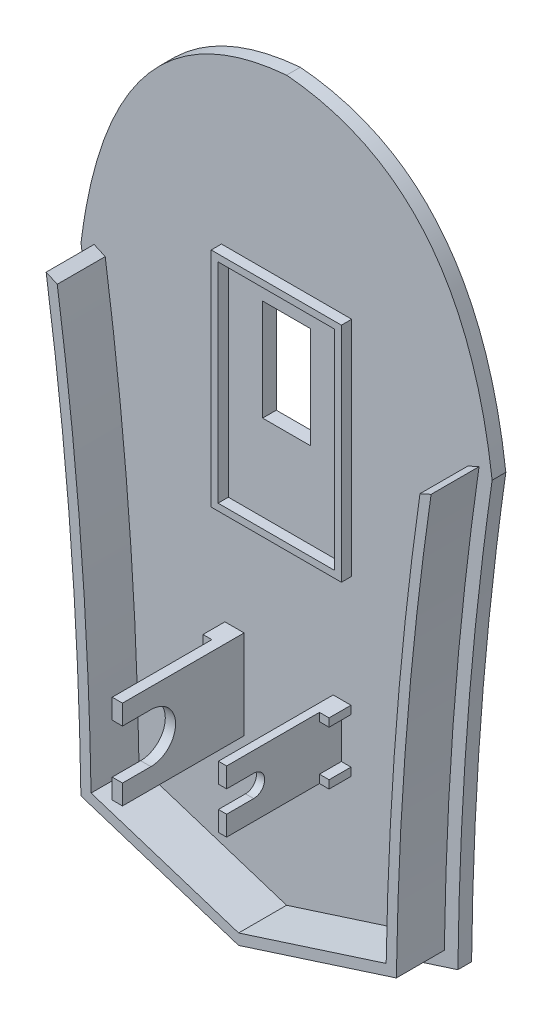
SolidWorks part; units mm, degrees
ref_plane "Přední rovina" through (0, 0, 0) normal (0, 0, 1) x (1, 0, 0)
ref_plane "Horní rovina" through (0, 0, 0) normal (0, 1, 0) x (1, 0, 0)
ref_plane "Pravá rovina" through (0, 0, 0) normal (1, 0, 0) x (0, 0, -1)
sketch "Skica3" plane through (0, 0, 0) normal (0, 0, 1) x (1, 0, 0)
  line L0 (0, 108.5972) -> (0, 0) construction
  line L1 (0, 0) -> (25, 8.0276)
  line L2 (0, 0) -> (-25, 8.0276)
  spline S0 degree 2 poles (25, 8.0276) (25.363, 40.4056) (30, 72.3988) knots 0 0 0 1 1 1
  spline S1 degree 2 poles (30, 72.3988) (25.8102, 106.3932) (0, 108.5972) knots 0 0 0 1 1 1
  spline S2 degree 2 poles (-25, 8.0276) (-25.363, 40.4056) (-30, 72.3988) knots 0 0 0 1 1 1
  spline S3 degree 2 poles (-30, 72.3988) (-25.8102, 106.3932) (0, 108.5972) knots 0 0 0 1 1 1
  dimension "D1" = 36.1984
  dimension "D2" = 62.7645
  dimension "D3" = 100.5695
  dimension "D4" = 108.5972
  dimension "D5" = 60
  dimension "D6" = 50
  dimension "D7" = 55
  dimension "D8" = 7.7177
  dimension "D9" = 1.523
extrude "Přidat vysunutím3" add sketch "Skica3" along normal blind 2
sketch "Skica5" plane through (0, 0, 2) normal (0, 0, 1) x (1, 0, 0)
  line L0 (0, 69.8773) -> (0, 10) construction
  line L3 (-8.5, 81.5) -> (8.5, 81.5)
  line L4 (8.5, 81.5) -> (8.5, 51)
  line L5 (8.5, 51) -> (0, 51)
  line L6 (-9.5, 50) -> (9.5, 50)
  line L7 (9.5, 50) -> (9.5, 82.5)
  line L8 (9.5, 82.5) -> (-9.5, 82.5)
  line L9 (-9.5, 50) -> (-9.5, 82.5)
  line L10 (-8.5, 51) -> (0, 51)
  line L11 (-8.5, 81.5) -> (-8.5, 51)
  point P6 (0, 82.5)
  point P12 (4.25, 51)
  point P15 (9.5, 66.25)
  point P19 (0, 50)
  point P20 (0, 81.5)
  dimension "D1" = 1
  dimension "D2" = 1
  dimension "D3" = 1
  dimension "D4" = 9.5
  dimension "D5" = 32.5
  dimension "D6" = 50
sketch "Skica6" plane through (0, 0, 2) normal (0, 0, 1) x (1, 0, 0)
  line L0 (-9.5, 50) -> (9.5, 50) construction
  line L1 (8, 33.66) -> (8, 24.66)
  line L2 (8, 33.66) -> (6.8, 33.66)
  line L3 (6.8, 33.66) -> (6.8, 24.66)
  line L4 (8, 24.66) -> (6.8, 24.66)
  line L5 (-6.2, 35) -> (-6.2, 22)
  line L6 (-6.2, 35) -> (-7.7, 35)
  line L7 (-7.7, 35) -> (-7.7, 22)
  line L8 (-6.2, 22) -> (-7.7, 22)
  line L9 (-9.5, 50) -> (-9.5, 82.5) construction
  line L10 (9.5, 50) -> (9.5, 82.5) construction
  point P15 (7.4, 24.66)
  dimension "D2" = 13
  dimension "D3" = 9
  dimension "D4" = 16.34
  dimension "D5" = 1.2
  dimension "D6" = 15
  dimension "D7" = 3.3
  dimension "D8" = 1.5
  dimension "D9" = 2.7
  dimension "D10" = 2.1
  dimension "D11" = 28
extrude "Přidat vysunutím4" add sketch "Skica5" along normal blind 1.5
extrude "Přidat vysunutím5" add sketch "Skica6" along normal blind 17.75 contours L5 L8 L7 L6
extrude "Přidat vysunutím6" add sketch "Skica6<4>" along normal blind 16.75 contours L4 L1 L2 L3 region at (7.4, 29.16, 2)
sketch "Skica6<4>" plane through (0, 0, 2) normal (0, 0, 1) x (1, 0, 0) same geometry as "Skica6"
sketch "Skica9" plane through (0, 0, 2) normal (0, 0, 1) x (1, 0, 0)
  line L0 (8, 33.66) -> (8, 24.66) construction
  line L1 (8, 33.66) -> (8, 32.4771)
  line L2 (8, 33.66) -> (9.4, 33.66)
  line L3 (9.4, 33.66) -> (9.4, 32.4771)
  line L4 (8, 32.4771) -> (9.4, 32.4771)
  line L5 (8, 24.66) -> (8, 25.8416)
  line L6 (8, 24.66) -> (9.4, 24.66)
  line L7 (9.4, 24.66) -> (9.4, 25.8416)
  line L8 (8, 25.8416) -> (9.4, 25.8416)
  line L9 (-7.7, 22) -> (-7.7, 23.3695)
  line L10 (-7.7, 22) -> (-9, 22)
  line L11 (-9, 22) -> (-9, 23.3695)
  line L12 (-7.7, 23.3695) -> (-9, 23.3695)
  line L13 (-7.7, 35) -> (-7.7, 33.66)
  line L14 (-7.7, 35) -> (-9, 35)
  line L15 (-9, 35) -> (-9, 33.66)
  line L16 (-7.7, 33.66) -> (-9, 33.66)
  line L18 (-7.7, 35) -> (-7.7, 22) construction
  line L19 (6.8, 33.66) -> (6.8, 24.66) construction
  line L20 (-7.7, 35) -> (-7.7, 22) construction
  dimension "D2" = 1.3
  dimension "D3" = 1.34
  dimension "D4" = 1.3
  dimension "D5" = 1.3695
  dimension "D6" = 1.4
  dimension "D7" = 1.1816
  dimension "D8" = 1.4
  dimension "D9" = 1.3
  dimension "D10" = 6.6355
  dimension "D11" = 10.2905
  dimension "D12" = 1.1829
  dimension "D13" = 1.4
  dimension "D14" = 25.8416
  dimension "D16" = 13
  dimension "D17" = 9
  dimension "D19" = 2.6
  dimension "D20" = 1.2
extrude "Přidat vysunutím7" add sketch "Skica9" along normal blind 3.2
sketch "Skica11" plane through (8, 0, 0) normal (1, 0, 0) x (0, 0, -1)
  line L0 (-18.75, 29.16) -> (-2, 29.1594) construction
  line L1 (-18.75, 33.66) -> (-18.75, 24.66) construction
  line L2 (-2, 32.4771) -> (-2, 25.8416) construction
  line L3 (-18.75, 27.56) -> (-18.75, 30.76)
  line L4 (-18.75, 30.76) -> (-14.8, 30.76)
  line L5 (-18.75, 27.56) -> (-14.8, 27.56)
  arc A0 (-14.8, 27.56) -> (-14.8, 30.76) centre (-14.8, 29.16) ccw
  point P8 (-13.2, 29.16)
  point P12 (-18.75, 29.16)
  dimension "D1" = 3.2
  dimension "D2" = 11.2
extrude "Odebrat vysunutím5" cut sketch "Skica11" against normal up to surface (1.2 mm away) up to face at (6.8, 29.16, 10.375)
sketch "Skica12" plane through (-7.7, 0, 0) normal (-1, 0, 0) x (0, 0, 1)
  line L0 (19.75, 32.1) -> (19.75, 24.9)
  line L1 (19.75, 35) -> (19.75, 22) construction
  line L2 (19.75, 24.9) -> (15.6, 24.9)
  line L3 (19.75, 32.1) -> (15.6, 32.1)
  line L4 (2, 33.66) -> (2, 23.3695) construction
  arc A0 (15.6, 32.1) -> (15.6, 24.9) centre (15.6, 28.5) ccw
  point P4 (19.75, 28.5)
  point P5 (19.75, 28.5)
  point P9 (12, 28.5)
  dimension "D2" = 10
  dimension "D1" = 7.2
extrude "Odebrat vysunutím6" cut sketch "Skica12" against normal up to surface (1.5 mm away) up to face at (-6.2, 28.5, 10.875)
sketch "Skica13" plane through (0, 0, 2) normal (0, 0, 1) x (1, 0, 0)
  line L0 (8.5, 81.5) -> (-8.5, 81.5) construction
  line L1 (-3.5, 78.3) -> (3.5, 78.3)
  line L2 (-3.5, 78.3) -> (-3.5, 63.5)
  line L3 (-3.5, 63.5) -> (3.5, 63.5)
  line L4 (3.5, 78.3) -> (3.5, 63.5)
  line L5 (8.5, 81.5) -> (-8.5, 81.5) construction
  point P6 (0, 81.5)
  point P9 (0, 78.3)
  dimension "D1" = 7
  dimension "D2" = 14.8
  dimension "D3" = 3.2
extrude "Odebrat vysunutím7" cut sketch "Skica13" against normal up to surface (2 mm away) up to face at (4.1667, 44.9083, 0)
sketch "Skica15" plane through (0, 0, 2) normal (0, 0, 1) x (1, 0, 0)
  line L2 (-23.0172, 9.4915) -> (0, 2.1006)
  line L3 (0, 2.1006) -> (23.0172, 9.4915)
  line L4 (-21.535, 10.591) -> (0, 3.676)
  line L5 (0, 3.676) -> (21.535, 10.591)
  line L6 (-21.535, 10.591) -> (0, 3.676)
  line L7 (0, 3.676) -> (21.535, 10.591)
  line L8 (26.4683, 72.431) -> (28.0881, 73.1557)
  line L9 (-28.0881, 73.1557) -> (-26.4683, 72.431)
  line L10 (-9.5, 82.5) -> (-9.5, 50) construction
  line L11 (0, 90.0139) -> (-26.4683, 72.431) construction
  line L12 (0, 91.8147) -> (-28.0881, 73.1557) construction
  line L13 (26.4683, 72.431) -> (0, 90.0139) construction
  line L14 (28.0881, 73.1557) -> (0, 91.8147) construction
  line L15 (9.5, 82.5) -> (-9.5, 82.5) construction
  spline S0 degree 3 poles (1457.059, -1319.3942) (-474.7142, -342.4138) (-508.3658, 483.1418) (1669.7898, 1132.2482) knots -19.530705 -19.530705 -19.530705 -19.530705 20.136227 20.136227 20.136227 20.136227 only from (21.535, 10.591) to (26.4683, 72.431)
  spline S1 degree 3 poles (1026.4591, 68.9197) (-95.6954, -130.1633) (42.7845, -6.071) (25.1499, 79.9688) (24.6899, 81.8198) (23.8494, 84.5578) (23.544, 85.464) (22.8741, 87.2612) (22.5084, 88.155) (21.3151, 90.7894) (20.3982, 92.472) (18.7858, 94.8519) (18.2086, 95.621) (16.9617, 97.1031) (16.3026, 97.803) (14.2209, 99.7665) (12.691, 100.8971) (10.59, 102.0736) (10.1587, 102.2978) (9.2874, 102.7176) (8.8472, 102.9134) (7.5137, 103.4609) (5.701, 104.0845) (3.8264, 104.5171) (-53.4182, 114.9439) (-140.259, -29.2015) (760.2714, 754.665) knots -5.499281 -5.499281 -5.499281 -5.499281 0.125 0.125 0.25 0.25 0.3125 0.3125 0.375 0.375 0.5 0.5 0.5625 0.5625 0.625 0.625 0.75 0.75 0.78125 0.78125 0.8125 0.8125 0.875 0.9375 0.9375 4.635987 4.635987 4.635987 4.635987 only from (26.4683, 72.431) to (0, 90.0139)
  spline S2 degree 3 poles (-52.9805, 1103.6787) (175.6151, -84.1208) (57.0864, 121.956) (-6.5822, 103.7808) (-7.4913, 103.4693) (-8.8342, 102.9191) (-9.2794, 102.7212) (-10.1496, 102.3024) (-10.5762, 102.0809) (-12.6661, 100.9128) (-14.2006, 99.7844) (-16.3, 97.806) (-16.969, 97.0947) (-18.2091, 95.62) (-18.7847, 94.8534) (-19.8583, 93.2692) (-20.3563, 92.4516) (-21.2842, 90.7715) (-21.7148, 89.9073) (-22.9107, 87.266) (-23.5698, 85.4685) (-24.6896, 81.8208) (-25.1495, 79.9705) (-42.846, -6.36) (96.4089, -132.3477) (-1026.4537, 76.4262) knots -4.132369 -4.132369 -4.132369 -4.132369 0.125 0.125 0.1875 0.1875 0.21875 0.21875 0.25 0.25 0.375 0.375 0.4375 0.4375 0.5 0.5 0.5625 0.5625 0.625 0.625 0.75 0.75 0.875 0.875 6.518822 6.518822 6.518822 6.518822 only from (0, 90.0139) to (-26.4683, 72.431)
  spline S3 degree 3 poles (-1669.816, 1132.256) (508.3537, 483.1521) (474.7223, -342.4006) (-1457.0261, -1319.3776) knots -19.136386 -19.136386 -19.136386 -19.136386 20.53048 20.53048 20.53048 20.53048 only from (-26.4683, 72.431) to (-21.535, 10.591)
  spline S4 degree 3 poles (21.535, 10.591) (21.8733, 31.3085) (23.516, 51.922) (26.4683, 72.431) knots 0 0 0 0 1 1 1 1
  spline S7 degree 3 poles (-26.4683, 72.431) (-23.516, 51.922) (-21.8733, 31.3085) (-21.535, 10.591) knots 0 0 0 0 1 1 1 1
  spline S8 degree 1 poles (-28.0881, 73.1557) (-23.0172, 9.4915) knots 0 0 1 1 construction
  spline S9 degree 1 poles (23.0172, 9.4915) (28.0881, 73.1557) knots 0 0 1 1 construction
  spline S12 degree 3 poles (-28.0881, 73.1557) (-27.3288, 67.8811) (-25.9473, 57.3053) (-24.4274, 41.4137) (-23.4129, 25.4819) (-23.1042, 14.82) (-23.0172, 9.4915) knots -0.015254 -0.015254 -0.015254 -0.015254 0.242884 0.501021 0.759159 1.017296 1.017296 1.017296 1.017296
  spline S13 degree 3 poles (23.0172, 9.4915) (23.1042, 14.82) (23.4129, 25.4819) (24.4274, 41.4137) (25.9473, 57.3053) (27.3288, 67.8811) (28.0881, 73.1557) knots -0.017296 -0.017296 -0.017296 -0.017296 0.240841 0.498979 0.757116 1.015254 1.015254 1.015254 1.015254
  point P6 (-15.9376, 72.8985)
  point P12 (5.1016, 104.5082)
  dimension "D3" = 14.6016
  dimension "D4" = 37.5881
  dimension "D5" = 6.4376
  dimension "D6" = 22.0082
  dimension "D7" = 9.6015
  dimension "D1" = 3.5
  dimension "D2" = 1.5
extrude "Přidat vysunutím9" add sketch "Skica15" along normal blind 7
